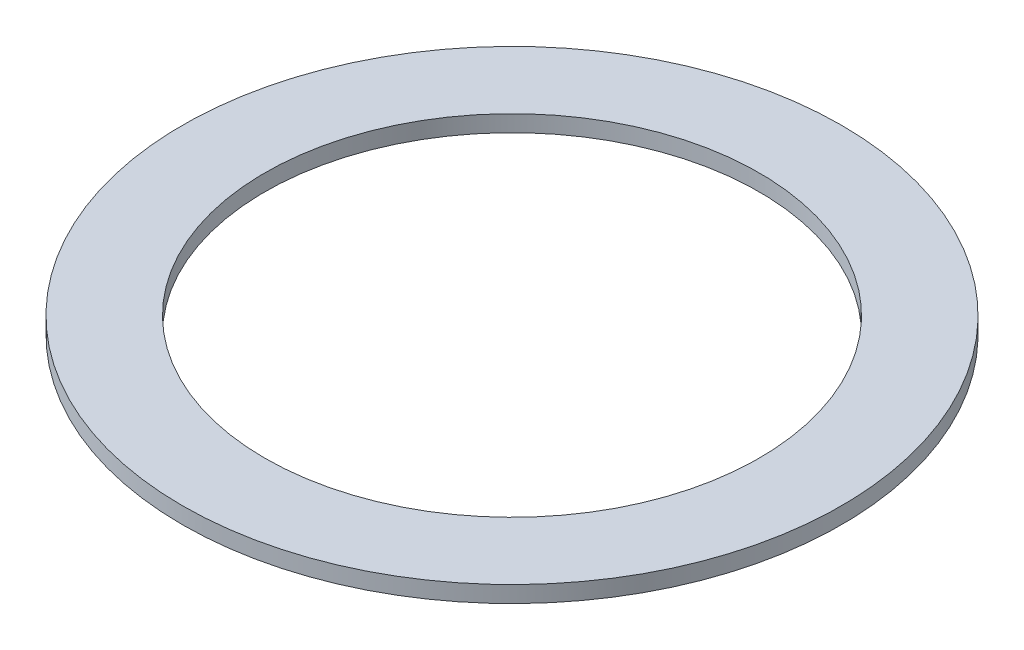
SolidWorks part; units mm, degrees
ref_plane "Front Plane" through (0, 0, 0) normal (0, 0, 1) x (1, 0, 0)
ref_plane "Top Plane" through (0, 0, 0) normal (0, 1, 0) x (1, 0, 0)
ref_plane "Right Plane" through (0, 0, 0) normal (1, 0, 0) x (0, 0, -1)
sketch "Sketch1" plane through (0, 0, 0) normal (0, 1, 0) x (1, 0, 0)
  circle A0 centre (0, 0) radius 3.5
  circle A1 centre (0, 0) radius 2.5
  dimension "D1" = 7
  dimension "D2" = 5
extrude "Boss-Extrude1" [suppressed] add sketch "Sketch1" along normal blind 6
sketch "Sketch2" plane through (0, 0, 0) normal (0, 1, 0) x (1, 0, 0)
  circle A0 centre (0, 0) radius 7.5
  circle A1 centre (0, 0) radius 10
  dimension "D1" = 15
  dimension "D2" = 20
extrude "Boss-Extrude2" add sketch "Sketch2" along normal blind 0.5
